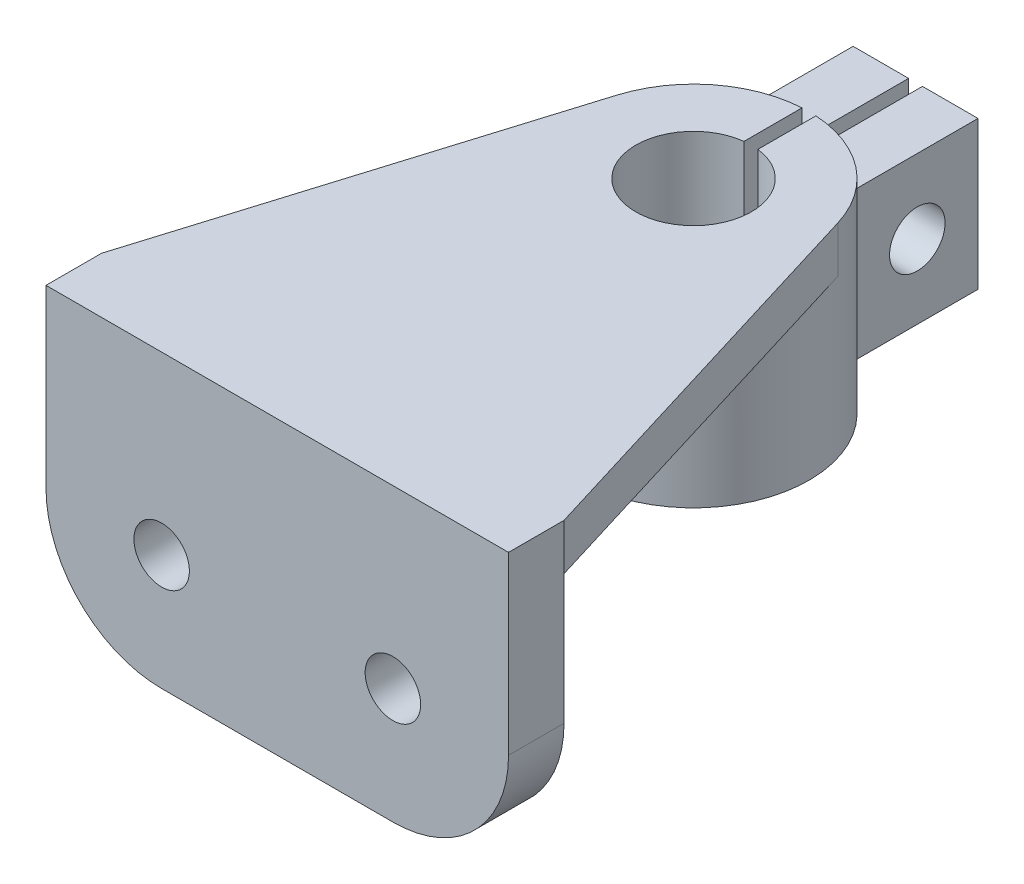
SolidWorks part; units mm, degrees
note: The reader was unsure of these and kept them because the rebuilt part matched: shared geometry of "Sketch4<3>".
ref_plane "Front Plane" through (0, 0, 0) normal (0, 0, 1) x (1, 0, 0)
ref_plane "Top Plane" through (0, 0, 0) normal (0, 1, 0) x (1, 0, 0)
ref_plane "Right Plane" through (0, 0, 0) normal (1, 0, 0) x (0, 0, -1)
sketch "Sketch1" plane through (0, 0, 0) normal (0, 0, 1) x (1, 0, 0)
  line L1 (25, -31.5) -> (-25, -31.5)
  line L2 (50, -6.5) -> (50, 31.5)
  line L3 (50, 31.5) -> (-50, 31.5)
  line L4 (-50, -6.5) -> (-50, 31.5)
  line L5 (50, -31.5) -> (-50, 31.5) construction
  line L6 (50, 31.5) -> (-50, -31.5) construction
  arc A0 (25, -31.5) -> (50, -6.5) centre (25, -6.5) ccw
  arc A1 (-25, -31.5) -> (-50, -6.5) centre (-25, -6.5) cw
  point P0 (0, 0)
  dimension "D3" = 25
  dimension "D1" = 100
  dimension "D2" = 63
extrude "Boss-Extrude1" add sketch "Sketch1" along normal blind 12
sketch "Sketch3" plane through (0, 0, 12) normal (0, 0, 1) x (1, 0, 0)
  circle A0 centre (-25, -6.5) radius 6
  circle A1 centre (25, -6.5) radius 6
  dimension "D1" = 12
extrude "Cut-Extrude1" cut sketch "Sketch3" against normal blind 12
sketch "Sketch4" plane through (0, 31.5, 0) normal (0, 1, 0) x (1, 0, 0)
  line L0 (0, -12) -> (0, 78) construction
  line L1 (50, -12) -> (-50, -12) construction
  line L2 (-50, 0) -> (-23.9068, 85.312)
  line L3 (23.9068, 85.312) -> (50, 0)
  line L4 (50, 0) -> (-50, 0) construction
  circle A0 centre (0, 78) radius 25
  point P13 (0, 0)
  point P14 (25, 78)
  dimension "D1" = 50
  dimension "D2" = 90
extrude "Boss-Extrude2" add sketch "Sketch4" against normal blind 10
extrude "Boss-Extrude3" add sketch "Sketch4<3>" against normal blind 44 contours A0
sketch "Sketch4<3>" plane through (0, 31.5, 0) normal (0, 1, 0) x (1, 0, 0) same geometry as "Sketch4"
sketch "Sketch6" plane through (0, -12.5, 0) normal (0, -1, 0) x (1, 0, 0)
  circle A1 centre (0, -78) radius 12.5
  dimension "D1" = 25
extrude "Cut-Extrude2" cut sketch "Sketch6" against normal blind 44
ref_plane "Plane1" through (0, 0, -126) normal (0, 0, -1) x (-1, 0, 0)
sketch "Sketch7" plane through (0, 0, -126) normal (0, 0, -1) x (-1, 0, 0)
  line L0 (0, 0) -> (0, 31.5) construction
  line L1 (23.9068, 31.5) -> (-23.9068, 31.5) construction
  line L3 (13.5, -6.5) -> (-13.5, -6.5)
  line L4 (13.5, -6.5) -> (13.5, 25.5)
  line L5 (13.5, 25.5) -> (-13.5, 25.5)
  line L6 (-13.5, -6.5) -> (-13.5, 25.5)
  line L7 (13.5, -6.5) -> (-13.5, 25.5) construction
  line L8 (13.5, 25.5) -> (-13.5, -6.5) construction
  point P5 (0, 9.5)
  dimension "D1" = 32
  dimension "D2" = 27
  dimension "D3" = 6
extrude "Boss-Extrude4" add sketch "Sketch7" against normal up to next
sketch "Sketch8" plane through (0, -12.5, 0) normal (0, -1, 0) x (1, 0, 0)
  line L0 (0, -90.5) -> (0, -126)
  line L1 (-29.15, -126) -> (29.15, -126) construction
  line L3 (1.5, -126.3156) -> (-1.5, -126.3156)
  line L4 (1.5, -126.3156) -> (1.5, -72.6446)
  line L5 (1.5, -72.6446) -> (-1.5, -72.6446)
  line L6 (-1.5, -126.3156) -> (-1.5, -72.6446)
  line L7 (1.5, -126.3156) -> (-1.5, -72.6446) construction
  line L8 (1.5, -72.6446) -> (-1.5, -126.3156) construction
  circle A0 centre (0, -78) radius 12.5 construction
  point P7 (0, -99.4801)
extrude "Cut-Extrude3" cut sketch "Sketch8" against normal blind 44 and the other way through all contours L6 L5 L4 L3
sketch "Sketch9" plane through (-13.5, 0, 0) normal (-1, 0, 0) x (0, 0, 1)
  line L1 (-99.0416, 25.5) -> (-126, 25.5) construction
  circle A0 centre (-112.8744, 9.5) radius 6
  point P6 (-113.1573, -4.1541)
  dimension "D1" = 12
  dimension "D2" = 16
extrude "Cut-Extrude4" cut sketch "Sketch9" against normal blind 44
sketch "Sketch10" plane through (0, 0, 0) normal (1, 0, 0) x (0, 0, -1)
  line L0 (53, -12.5) -> (0, -31.5)
  line L1 (0, -31.5) -> (0, 21.5)
  line L2 (0, 21.5) -> (53, 21.5)
  line L3 (53, 21.5) -> (53, -12.5) construction
  line L4 (53, 21.5) -> (53, -12.5)
  point P4 (53, -12.5)
extrude "Boss-Extrude8" add sketch "Sketch10" along normal mid plane 5 separate body
sketch "Sketch11" plane through (0, 0, -53) normal (0, 0, -1) x (-1, 0, 0)
  line L4 (2.5, -12.5) -> (2.5, 21.5)
  line L5 (2.5, 21.5) -> (-2.5, 21.5)
  line L6 (-2.5, 21.5) -> (-2.5, -12.5)
  line L7 (-2.5, -12.5) -> (2.5, -12.5)
  line L8 (2.5, -12.5) -> (2.5, 21.5)
  line L9 (2.5, 21.5) -> (-2.5, 21.5)
  line L10 (-2.5, 21.5) -> (-2.5, -12.5)
  line L11 (-2.5, -12.5) -> (2.5, -12.5)
  dimension "D1" = 0
extrude "Boss-Extrude9" add sketch "Sketch11" along normal up to surface up to face at (0, 13.75, -93.0552)
